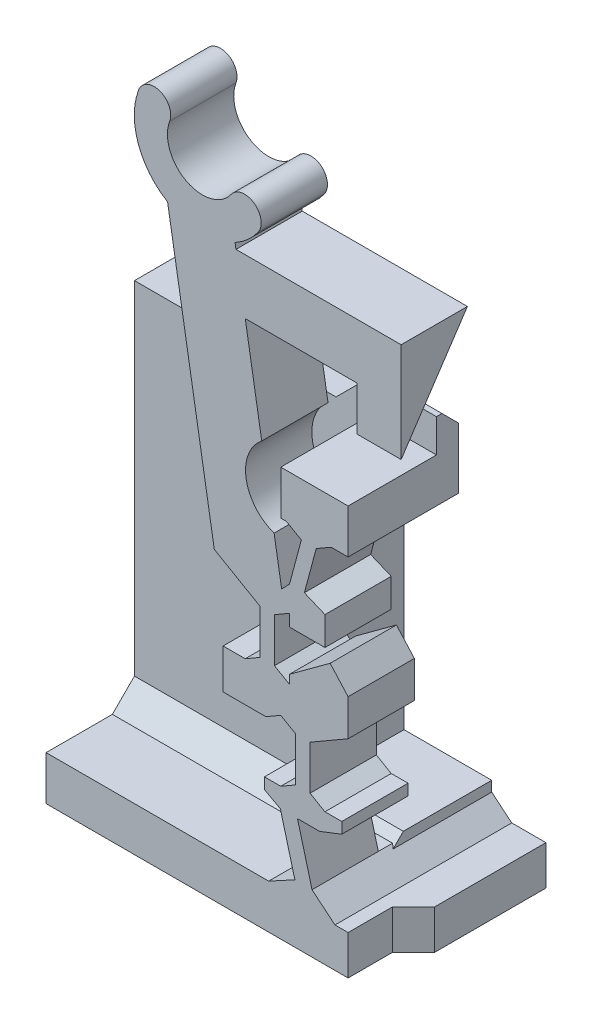
SolidWorks part; units mm, degrees
material "Nylon 6/12"
ref_plane "Front Plane" through (0, 0, 0) normal (0, 0, 1) x (1, 0, 0)
ref_plane "Top Plane" through (0, 0, 0) normal (0, 1, 0) x (1, 0, 0)
ref_plane "Right Plane" through (0, 0, 0) normal (1, 0, 0) x (0, 0, -1)
sketch "Sketch-SkeletonConfigUp" plane through (0, 0, 0) normal (0, 0, 1) x (1, 0, 0)
  line L0 (0, 0) -> (0, -50000) construction
  line L1 (0, 0) -> (4.5811, 6.2164) construction
  line L2 (9.8143, 13.3177) -> (4.5811, 13.945) construction
  line L3 (4.5811, 13.945) -> (2.9713, 10.4094) construction
  line L4 (2.9713, 10.4094) -> (4.5811, 6.2164) construction
  line L5 (4.5811, 13.945) -> (6.2429, 19.1409) construction
  line L6 (2.9713, 10.4094) -> (0.0405, 27.8193) construction
  line L7 (4.5811, 6.2164) -> (9.8143, 13.3177) construction
  line L8 (-587.3593, -797.0242) -> (9.8143, 13.3177) construction
  dimension "D2" = 7.7221
  dimension "D3" = 8.8212
  dimension "D4" = 5.2707
  dimension "D5" = 119.553
  dimension "D6" = 3.8848
  dimension "D7" = 5.4552
  dimension "D8" = 17.6549
  dimension "D9" = 4.4914
  dimension "D10" = 6.745
  dimension "D11" = 145.964
  dimension "D12" = 143.612
sketch "Sketch-SkeletonConfigDown" plane through (0, 0, 0) normal (0, 0, 1) x (1, 0, 0)
  line L0 (0, 0) -> (0, -50000) construction
  line L1 (0, 0) -> (4.5811, 6.2164) construction
  line L2 (9.8143, 13.3177) -> (4.5811, 13.945) construction
  line L3 (4.5811, 13.945) -> (6.1909, 10.4094) construction
  line L4 (6.1909, 10.4094) -> (4.5811, 6.2164) construction
  line L5 (4.5811, 13.945) -> (1.753, 18.6098) construction
  line L6 (6.1909, 10.4094) -> (-8.8652, 19.6294) construction
  line L7 (4.5811, 6.2164) -> (9.8143, 13.3177) construction
  line L8 (-589.9357, -800.5203) -> (9.8143, 13.3177) construction
  dimension "D2" = 7.7221
  dimension "D3" = 8.8212
  dimension "D4" = 5.2707
  dimension "D5" = 119.553
  dimension "D6" = 3.8848
  dimension "D7" = 5.4552
  dimension "D8" = 17.6549
  dimension "D9" = 4.4914
  dimension "D10" = 6.745
  dimension "D11" = 145.964
  dimension "D1" = 143.612
ref_plane "Plane-Cam Base" through (9.128, 0, 0) normal (1, 0, 0) x (0, 0, -1)
ref_plane "Plane-Down-to-Up Derailleur Clearance" through (6.628, 0, 0) normal (1, 0, 0) x (0, 0, -1)
ref_plane "Plane-Cam Cavity Roof" through (5.128, 0, 0) normal (1, 0, 0) x (0, 0, -1)
sketch "Sketch-SwitchBossUp" plane through (0, 0, 0) normal (0, 0, 1) x (1, 0, 0)
  line L0 (3.5811, 11.4759) -> (3.5811, 12.945) construction
  line L5 (5.5811, 12.5552) -> (5.5811, 11.263)
  line L7 (1.5115, 25.1048) -> (1.5536, 24.8548)
  line L8 (-0.4607, 24.7728) -> (1.6966, 11.9577) construction
  line L9 (2.9713, 10.4094) -> (0.0405, 27.8193) construction
  line L11 (0.1364, 21.2256) -> (2.1086, 21.5576) construction
  line L15 (6.628, -23.7286) -> (6.628, 23.7286) construction
  line L16 (2.9713, 10.4094) -> (4.5811, 6.2164) construction
  line L17 (3.5811, 12.945) -> (3.5811, 14.945) construction
  line L18 (5.5811, 12.945) -> (5.5811, 14.945) construction
  line L19 (4.2561, 13.945) -> (4.9061, 13.945) construction
  line L20 (3.5811, 14.945) -> (5.5811, 14.945) construction
  line L21 (3.5811, 12.945) -> (5.5811, 12.945) construction
  line L22 (4.5811, 12.945) -> (4.5811, 14.945) construction
  line L23 (4.5811, 6.2164) -> (8.5405, 7.1023) construction
  line L24 (1.9713, 9.4094) -> (1.9713, 11.4094) construction
  line L25 (3.9713, 9.4094) -> (3.9713, 11.4094) construction
  line L26 (3.9713, 9.4094) -> (1.9713, 9.4094) construction
  line L27 (1.9713, 11.4094) -> (3.9713, 11.4094) construction
  line L28 (3.5811, 7.2164) -> (5.5811, 7.2164) construction
  line L29 (3.5811, 7.2164) -> (3.5811, 5.2164) construction
  line L30 (5.5811, 7.2164) -> (5.5811, 5.2164) construction
  line L31 (3.5811, 5.2164) -> (5.5811, 5.2164) construction
  line L32 (4.9061, 6.2164) -> (4.2561, 6.2164) construction
  line L40 (3.2963, 10.4094) -> (2.6463, 10.4094) construction
  line L66 (0.0405, 27.8193) -> (0.0405, 50027.8193) construction
  line L75 (3.95, 3.937) -> (4.6085, 1.4797) construction
  line L76 (5.5811, 11.263) -> (5.5811, 12.5552) construction
  line L77 (5.5811, 7.6061) -> (6.628, 8.2105)
  line L80 (5.8152, 10.763) -> (6.628, 9.8603)
  line L81 (9.128, 1033.2419) -> (9.128, 20.0586) construction
  line L85 (6.9307, 9.5241) -> (8.5405, 7.7363) construction
  line L88 (5.7256, 17.3347) -> (6.628, 17.3347)
  line L92 (3.7762, 8.3129) -> (6.9307, 9.5241) construction
  line L98 (1.9713, 9.0197) -> (0.9713, 9.0197)
  line L99 (0.9713, 9.0197) -> (0.9713, 7.2164)
  line L100 (0.9713, 7.2164) -> (2.9061, 7.2164)
  line L101 (4.5811, 6.2164) -> (6.9307, 9.5241) construction
  line L103 (0.0405, 27.8193) -> (1.9448, 26.4638) construction
  line L104 (6.9307, 9.5241) -> (8.5405, 7.7363) construction
  line L107 (1.9713, 9.4094) -> (1.9713, 9.0197) construction
  line L109 (0.0405, 27.8193) -> (-2.1498, 28.6358) construction
  line L111 (6.628, 9.8603) -> (6.628, 8.2105)
  line L112 (6.628, 9.8603) -> (6.9307, 9.5241) construction
  line L113 (2.8424, 4.8267) -> (2.8424, 4.3267)
  line L114 (7.3693, 7.7363) -> (7.3563, 7.7363) construction
  line L121 (4.9967, -1.1226) -> (4.9967, 1.4797) construction
  line L122 (9.028, 22.3548) -> (9.028, 20.3548)
  line L127 (5.5811, 15.3347) -> (5.5811, 14.945) construction
  line L130 (6.0345, 0.6165) -> (6.628, 0.6165)
  line L132 (2.8424, 4.3267) -> (3.5618, 3.937)
  line L133 (2.9713, 10.4094) -> (6.1909, 10.4094) construction
  line L134 (4.5811, 10.4094) -> (4.5811, 13.945) construction
  line L135 (4.5811, 10.4094) -> (4.5811, 6.2164) construction
  line L137 (3.9713, 9.4094) -> (5.5811, 7.2164) construction
  line L139 (5.8152, 10.763) -> (3.9713, 9.4094)
  line L141 (4.2202, 1.4797) -> (3.0345, 0.8347)
  line L142 (3.0345, 0.8347) -> (3.0345, -1.1653)
  line L143 (9.128, 20.0586) -> (9.128, 18.3333) construction
  line L145 (9.128, 16.6071) -> (9.128, -49992.4167) construction
  line L147 (5.5811, 11.263) -> (5.5811, 12.5552) construction
  line L150 (3.0345, -1.1653) -> (6.628, -1.1653)
  line L151 (3.5618, 3.937) -> (4.3383, 3.937) construction
  line L152 (4.5126, 14.945) -> (3.9767, 12.945)
  line L153 (5.1855, 14.945) -> (4.6496, 12.945)
  line L157 (3.5811, 17.3347) -> (3.5811, 15.3347)
  line L158 (5.8605, 15.3347) -> (6.628, 15.3347)
  line L162 (3.2963, 11.4094) -> (3.2963, 9.4094)
  line L164 (2.6463, 11.4094) -> (2.6463, 9.4094)
  line L169 (4.2561, 7.2164) -> (4.2561, 5.2164)
  line L170 (4.9061, 5.2164) -> (4.9061, 7.2164)
  line L175 (4.2561, 7.2164) -> (3.5811, 7.6061)
  line L176 (4.9061, 7.2164) -> (5.5811, 7.6061)
  line L177 (5.5811, 7.2164) -> (5.5811, 7.6061) construction
  line L179 (4.2561, 5.2164) -> (3.5811, 4.8267)
  line L180 (3.5811, 5.2164) -> (3.5811, 4.8267) construction
  line L181 (3.5811, 4.8267) -> (2.8424, 4.8267)
  line L183 (4.9061, 5.2164) -> (5.5811, 4.8267)
  line L184 (5.5811, 5.2164) -> (5.5811, 4.8267) construction
  line L186 (9.128, -23.7286) -> (9.128, 23.7286) construction
  line L187 (2.6463, 9.4094) -> (1.9713, 9.0197)
  line L188 (3.2963, 9.4094) -> (3.9713, 9.0197)
  line L189 (3.2963, 11.4094) -> (3.9713, 11.7991)
  line L190 (2.6463, 11.4094) -> (1.6966, 11.9577)
  line L191 (3.9713, 11.4094) -> (3.9713, 11.7991) construction
  line L192 (3.9713, 11.7991) -> (3.9713, 11.263)
  line L193 (4.6496, 12.945) -> (5.5811, 12.5552)
  line L194 (3.9767, 12.945) -> (3.6203, 12.5779)
  line L195 (3.9713, 11.263) -> (5.5811, 11.263)
  line L196 (3.9713, 9.4094) -> (3.9713, 9.0197)
  line L197 (3.5811, 7.2164) -> (3.5811, 7.6061) construction
  line L199 (3.5811, 7.6061) -> (2.9061, 7.2164)
  line L201 (2.8424, 4.3267) -> (2.8424, 3.937) construction
  line L202 (2.8424, 3.937) -> (3.5618, 3.937) construction
  line L205 (3.0345, 1.4797) -> (3.0345, 0.8347) construction
  line L206 (4.9967, 1.4797) -> (6.0345, 0.6165)
  line L207 (9.128, 18.3333) -> (9.128, 16.6071) construction
  line L208 (6.628, -1.1653) -> (6.628, 0.6165)
  line L209 (9.128, 20.0586) -> (9.128, 16.6071) construction
  line L211 (4.9967, 1.4797) -> (4.3383, 3.937)
  line L212 (4.2202, 1.4797) -> (3.5618, 3.937)
  line L214 (4.5126, 14.945) -> (3.8375, 15.3347)
  line L215 (3.8375, 15.3347) -> (3.5811, 15.3347)
  line L216 (5.1855, 14.945) -> (5.8605, 15.3347)
  line L217 (5.5811, 12.945) -> (5.5811, 12.5552) construction
  line L218 (5.1855, 14.945) -> (5.1855, 15.3347) construction
  line L219 (5.8605, 15.3347) -> (3.8375, 15.3347) construction
  line L221 (9.028, 22.3548) -> (9.028, 24.8548)
  line L224 (3.5811, 17.3347) -> (5.7256, 17.3347)
  line L232 (6.628, 15.3347) -> (6.628, 17.3347)
  line L236 (1.5536, 24.8548) -> (9.028, 24.8548)
  line L240 (4.3383, 3.937) -> (5.3383, 3.937)
  line L241 (5.3383, 3.937) -> (6.3424, 4.3267)
  line L248 (7.028, 22.3548) -> (1.9744, 22.3548)
  line L249 (1.9744, 22.3548) -> (2.7198, 17.9273)
  line L250 (9.028, 20.3548) -> (7.028, 20.3548)
  line L251 (7.028, 20.3548) -> (7.028, 22.3548)
  line L252 (3.2801, 14.5986) -> (3.6203, 12.5779)
  line L253 (4.2672, 14.0291) -> (4.895, 13.8608) construction
  line L254 (4.9967, 1.4797) -> (4.2202, 1.4797) construction
  line L255 (4.2202, 1.4797) -> (3.0345, 1.4797) construction
  line L256 (1.6966, 11.9577) -> (0.5733, 12.6062)
  line L257 (0.5733, 12.6062) -> (-1.5413, 25.1678)
  line L367 (5.5811, 4.8267) -> (6.3424, 4.8267)
  line L368 (6.3424, 4.8267) -> (6.3424, 4.3267)
  arc A0 (1.5115, 25.1048) -> (2.5558, 26.0289) centre (0.0405, 27.8193) ccw
  arc A1 (-1.5413, 25.1678) -> (-2.8525, 28.8978) centre (0.0405, 27.8193) cw
  arc A2 (-2.8525, 28.8978) -> (-1.447, 28.3738) centre (-2.1498, 28.6358) cw
  arc A3 (2.5558, 26.0289) -> (1.3338, 26.8987) centre (1.9448, 26.4638) ccw
  arc A4 (-1.447, 28.3738) -> (1.3338, 26.8987) centre (0.0405, 27.8193) ccw
  arc A5 (3.5811, 12.945) -> (3.5811, 14.945) centre (3.1778, 13.945) ccw construction
  arc A6 (5.5811, 12.945) -> (5.5811, 14.945) centre (5.9843, 13.945) cw construction
  arc A7 (2.5293, 9.921) -> (1.9713, 11.4094) centre (1.568, 10.4094) ccw construction
  arc A8 (3.9713, 11.4094) -> (3.9713, 9.4094) centre (4.3745, 10.4094) ccw construction
  arc A9 (3.5811, 7.2164) -> (3.5811, 5.2164) centre (3.1779, 6.2164) cw construction
  arc A10 (5.5811, 7.2164) -> (5.5811, 5.2164) centre (5.9844, 6.2164) ccw construction
  circle A28 centre (0.0405, 27.8193) radius 2.3375 construction
  arc A29 (1.9713, 9.4094) -> (2.5293, 9.921) centre (1.568, 10.4094) ccw construction
  arc A30 (3.2801, 14.5986) -> (2.7198, 17.9273) centre (3.9114, 16.4164) cw
  arc A31 (-0.4607, 24.7728) -> (-1.5413, 25.1678) centre (0.0405, 27.8193) cw construction
  point P53 (4.5811, 13.945)
  point P63 (2.9713, 10.4094)
  point P93 (1.1225, 21.3916)
  dimension "D23" = 1.5875
  dimension "D24" = 0.75
  dimension "D2" = 2
  dimension "D5" = 2
  dimension "D8" = 42
  dimension "D16" = 42
  dimension "D27" = 120
  dimension "D28" = 120
  dimension "D29" = 120
  dimension "D30" = 120
  dimension "D31" = 120
  dimension "D32" = 120
  dimension "D33" = 120
  dimension "D34" = 120
  dimension "D17" = 0.5
  dimension "D21" = 2
  dimension "D38" = 2
  dimension "D39" = 0.5
  dimension "D40" = 60
  dimension "D41" = 1
  dimension "D42" = 45
  dimension "D43" = 120
  dimension "D10" = 15
  dimension "D25" = 15
  dimension "D26" = 120
  dimension "D35" = 120
  dimension "D20" = 3
  dimension "D48" = 2
  dimension "D82" = 1
  dimension "D83" = 3.5
  dimension "D14" = 2.5
  dimension "D15" = 0.25
  dimension "D7" = 2
  dimension "D9" = 2
  dimension "D6" = 0.65
  dimension "D12" = 0.75
  dimension "D13" = 1
extrude "Boss-Switch Body" add sketch "Sketch-SwitchBossUp" along normal blind 3
sketch "Sketch1" plane through (0, 0, 0) normal (0, 0, -1) x (-1, 0, 0)
  line L1 (-7.5811, -1.1653) -> (0.4122, -1.1653)
  line L2 (-7.5811, -1.1653) -> (-7.5811, 0.6165)
  line L4 (0.4122, -1.1653) -> (0.4122, 0.8347)
  line L5 (-3.5811, 18.8347) -> (-7.5811, 18.8347)
  line L10 (-7.5811, 18.8347) -> (-7.5811, 15.3347)
  line L11 (-4.2202, 1.4797) -> (-4.9967, 1.4797)
  line L12 (-7.5811, 15.3347) -> (-3.5811, 15.3347)
  line L13 (-4.2202, 1.4797) -> (-3.0345, 0.8347)
  line L14 (-3.5811, 15.3347) -> (-3.5811, 18.8347)
  line L20 (-4.3383, 3.937) -> (-4.9967, 1.4797) construction
  line L22 (-3.0345, -1.1653) -> (-6.628, -1.1653) construction
  line L23 (-3.0345, 0.8347) -> (0.4122, 0.8347)
  line L24 (-4.9967, 1.4797) -> (-6.0345, 0.6165)
  line L25 (-6.0345, 0.6165) -> (-7.5811, 0.6165)
  dimension "D1" = 3.5
extrude "Boss-Flange Width" add sketch "Sketch1" along normal blind 5
ref_plane "Plane-Sta2Sit Groove" through (0.0405, 0, 0) normal (1, 0, 0) x (0, 0, -1)
ref_plane "Plane-Cam Outer Surface" through (-12.0395, 0, 0) normal (1, 0, 0) x (0, 0, -1)
ref_plane "Plane-FlangeTop" through (-7.0395, 0, 0) normal (1, 0, 0) x (0, 0, -1)
sketch "Sketch2" plane through (-7.0395, 0, 0) normal (1, 0, 0) x (0, 0, -1)
  line L0 (5, 15.3347) -> (-3, 15.3347) construction
  line L1 (5, 17.3347) -> (1, 17.3347)
  line L2 (5, 17.3347) -> (5, 15.3347)
  line L3 (5, 15.3347) -> (1, 15.3347)
  line L4 (1, 17.3347) -> (1, 15.3347)
  line L5 (-3, -1.1653) -> (-3, 0.6165) construction
  line L11 (5, 0.8347) -> (-3, 0.8347)
  line L12 (5, 0.8347) -> (5, -1.1653)
  line L13 (5, -1.1653) -> (-3, -1.1653)
  line L14 (-3, 0.8347) -> (-3, -1.1653)
  line L15 (0, 10.4094) -> (0, 27.8193) construction
  line L17 (5, 0.6165) -> (5, -1.1653) construction
  line L18 (-3, 0.8347) -> (0, 0.8347) construction
  dimension "D1" = 1
  dimension "D2" = 2
extrude "Boss-Flange Height" add sketch "Sketch2" along normal up to surface (11.6675 mm away)
sketch "Sketch10" plane through (0, 15.3347, 0) normal (0, 1, 0) x (1, 0, 0)
  line L0 (9.128, -23.7286) -> (9.128, 23.7286) construction
  line L1 (7.5811, 5) -> (5.128, 5)
  line L2 (7.5811, 5) -> (7.5811, 2)
  line L3 (7.5811, 2) -> (5.128, 2)
  line L5 (4.628, 7) -> (4.628, 1) construction
  line L6 (3.5811, 1) -> (-7.0395, 1) construction
  line L8 (5.128, 5) -> (5.128, 2)
  dimension "D1" = 1
  dimension "D2" = 0.5
  dimension "D3" = 4.5
extrude "Cut-Up-To-Down Derailleur Clearance" cut sketch "Sketch10" along normal up to next
sketch "Sketch17" plane through (0, 15.3347, 0) normal (0, -1, 0) x (1, 0, 0)
  line L0 (5.128, -5) -> (-7.0395, -5)
  line L1 (5.128, -5) -> (-7.0395, -5) construction
  line L2 (-7.0395, -5) -> (-7.0395, -1)
  line L3 (-7.0395, -1) -> (5.128, -1)
  line L4 (5.128, -1) -> (5.128, -5)
  line L5 (-7.0395, -1) -> (-7.0395, -5) construction
extrude "Boss-Flange Support" add sketch "Sketch17" along normal up to surface (14.5 mm away) up to face at (-2.0025, 0.8347, -1)
sketch "Sketch-HolePositions" plane through (0, -1.1653, 0) normal (0, -1, 0) x (1, 0, 0)
  line L0 (-7.0395, -3) -> (7.5811, -3) construction
  line L1 (7.5811, -5) -> (-7.0395, -5) construction
  line L2 (7.5811, -5) -> (7.5811, 0) construction
  line L4 (-7.0395, -22.2167) -> (-7.0395, 22.2167) construction
  point P6 (-5.0395, -3)
  point P7 (-0.5395, -3)
  dimension "D1" = 2
  dimension "D2" = 4.5
  dimension "D3" = 2
sketch "Sketch6" plane through (0, -1.1653, 0) normal (0, -1, 0) x (-1, 0, 0)
  point P0 (5.0395, 3)
  point P3 (0.5395, 3)
hole_wizard "Tap Drill for M2x0.4 Tap1" positions "Sketch6" profile "Sketch5" hole size "M2x0.4" standard "ANSI Metric" end condition through all
sketch "Sketch5" plane through (-5.0395, -1.1653, -3) normal (1, 0, 0) x (0, 0, -1)
  line L0 (0, 0) -> (0, 30.5511)
  line L1 (0, 30.5511) -> (0.8, 30.5511)
  line L2 (0.8, 30.5511) -> (0.8, 0)
  line L5 (0.8, 0) -> (0, 0)
  line L11 (0, -6.35) -> (0, 107.95) construction
  dimension "Thru Hole Dia." = 1.6
  dimension "Thru Hole Depth" = 30.5511
sketch "Sketch9" plane through (0, -1.1653, 0) normal (0, -1, 0) x (1, 0, 0)
  point P0 (-5.0395, -3)
  point P3 (-0.5395, -3)
hole_wizard "M2 Clearance Hole2" positions "Sketch9" profile "Sketch8" hole size "M2" standard "ANSI Metric"
sketch "Sketch8" plane through (-5.0395, -1.1653, -3) normal (1, 0, 0) x (0, 0, -1)
  line L0 (0, 0) -> (0, 15.721)
  line L1 (0, 15.721) -> (1.2, 15)
  line L2 (1.2, 15) -> (1.2, 0)
  line L5 (1.2, 0) -> (0, 0)
  line L10 (0, 15.721) -> (-1.2, 15) construction
  line L11 (0, -6.35) -> (0, 107.95) construction
  dimension "Hole Dia." = 2.4
  dimension "Hole Depth" = 15
  dimension "Drill Angle" = 118
sketch "Sketch-Measurements for Derailleur Ramps" [suppressed] plane through (0, 0, 0) normal (0, 0, 1) x (1, 0, 0)
  line L0 (3.184, 15.1695) -> (2.4687, 19.4188)
  line L1 (2.8264, 17.2941) -> (1.8402, 17.1281)
  line L2 (2.9713, 10.4094) -> (0.0405, 27.8193) construction
  line L3 (1.8402, 17.1281) -> (-1.3081, 15.0016)
  line L4 (6.1909, 10.4094) -> (-8.8652, 19.6294) construction
  line L5 (1.8402, 17.1281) -> (2.6012, 12.6077)
  line L6 (2.6012, 12.6077) -> (-1.3081, 15.0016)
  line L7 (0.2661, 16.0649) -> (0.2661, 17.1281)
  line L8 (0.2661, 17.1281) -> (1.8402, 17.1281)
  line L9 (6.1909, 10.4094) -> (2.9713, 10.4094)
  line L10 (5.386, 8.3129) -> (3.7762, 8.3129)
  line L11 (2.6116, 18.5698) -> (1.5115, 25.1048) construction
  line L12 (6.1909, 10.4094) -> (4.5811, 6.2164) construction
  line L13 (4.5811, 8.3129) -> (4.5811, 8.7912)
  line L14 (4.5811, 6.2164) -> (5.386, 8.3129)
  line L15 (2.9713, 10.4094) -> (4.5811, 6.2164) construction
  line L16 (3.7762, 8.3129) -> (4.5811, 6.2164)
  line L17 (5.386, 8.3129) -> (5.386, 8.7912)
  dimension "D1" = 1.5742
  dimension "D2" = 0.8049
ref_plane "Plane1" through (0, 7.1023, 0) normal (0, 1, 0) x (1, 0, 0)
ref_plane "Plane-Cantilever Cut" [suppressed] through (7.0848, 8.5204, -1.9058) normal (-0.6301, -0.7578, 0.1695) x (-0.7765, 0.6151, -0.1368)
sketch "Sketch14" [suppressed] plane through (7.0848, 8.5204, -1.9058) normal (-0.6301, -0.7578, 0.1695) x (-0.7765, 0.6151, -0.1368)
  line L0 (2.3023, -1.6911) -> (-0.3551, -1.6911)
  line L2 (2.3023, -4.3362) -> (2.3023, -1.6911)
  line L3 (-0.3551, -1.6911) -> (-0.3551, -4.4608)
  line L5 (-0.3551, -4.4608) -> (1.0087, -5.0843)
  line L6 (1.0087, -5.0843) -> (2.3023, -4.3362)
extrude "Cut-Down-to-Up Cantilever Slope" [suppressed] cut sketch "Sketch14" against normal up to next
ref_plane "Plane-Symmetry Plane" through (0, 0, 1.5) normal (0, 0, 1) x (1, 0, 0)
sketch "Sketch-Cable Center Point" plane through (0, 0, 1.5) normal (0, 0, 1) x (1, 0, 0)
  line L0 (0.0405, 27.8193) -> (0.1722, 27.0366)
  line L1 (2.9713, 10.4094) -> (0.0405, 27.8193) construction
  point P0 (0.0405, 27.8193)
  dimension "D1" = 0.7937
chamfer "Chamfer-Flange Support" distance 1.5 angle 45 1 edges at (3.5811, 17.3347, -3)
chamfer "Chamfer-Flange Support 2" distance 1.5 angle 45 2 edges at (5.128, 17.0847, -2) (5.128, 15.3347, -1.5)
chamfer "Chamfer-Flange Support 3" distance 1 angle 45 1 edges at (-2.0025, 0.8347, -1)
chamfer "Chamfer7" [suppressed] distance 1 angle 45
sketch "Sketch23" plane through (0, 0, -1) normal (0, 0, 1) x (1, 0, 0)
  line L0 (5.128, 1.8347) -> (1.1605, 1.8347)
  line L1 (-7.0395, 1.8347) -> (5.128, 1.8347) construction
  line L2 (1.1605, 1.8347) -> (1.1605, 13.8347)
  line L3 (1.1605, 13.8347) -> (5.128, 13.8347)
  line L4 (5.128, 13.8347) -> (5.128, 1.8347)
  line L5 (0.6605, -1.1653) -> (0.6605, 13.8347) construction
  dimension "D1" = 0.5
extrude "Cut-Gap for Printing" cut sketch "Sketch23" against normal through all
sketch "Sketch25" plane through (0, 0, 0) normal (0, 0, 1) x (1, 0, 0)
  line L0 (6.628, 15.3347) -> (7.5811, 15.3347)
  line L1 (7.5811, 15.3347) -> (7.5811, 18.8347)
  line L2 (7.5811, 18.8347) -> (6.628, 18.8347)
  line L3 (6.628, -23.7286) -> (6.628, 23.7286) construction
  line L4 (7.5811, 18.8347) -> (3.5811, 18.8347) construction
  line L5 (6.628, 18.8347) -> (6.628, 15.3347)
  line L6 (7.5811, 18.8347) -> (7.5811, 15.3347) construction
extrude "Cut-Derailleur Clearance" cut sketch "Sketch25" against normal through all
chamfer "Chamfer8" distance 1 angle 45 1 edges at (6.628, -0.2744, 0)
ref_plane "Plane2" through (-3.0866, 5.589, 8.3835) normal (0.2929, -0.5304, -0.7956) x (-0.9561, -0.1625, -0.2437)
sketch "Sketch26" plane through (-3.0866, 5.589, 8.3835) normal (0.2929, -0.5304, -0.7956) x (-0.9561, -0.1625, -0.2437)
  line L0 (-7.553, 20.6804) -> (-7.553, 14.9094)
  line L1 (-12.6703, 20.6804) -> (-5.5238, 20.6804) construction
  line L3 (-7.553, 14.9094) -> (-20.0302, 14.9094)
  line L4 (-20.0302, 14.9094) -> (-20.0302, 20.6804)
  line L5 (-20.0302, 20.6804) -> (-7.553, 20.6804)
extrude "Cut-Up-to-Down Cantilever Slope" cut sketch "Sketch26" along normal up to next
sketch "Sketch27" plane through (5.128, 0, 0) normal (1, 0, 0) x (0, 0, -1)
  line L0 (3.5, 18.8347) -> (3.5, 13.8347) construction
  line L1 (2.5, 18.8347) -> (5, 18.8347)
  line L2 (2.5, 18.8347) -> (2.5, 13.8347)
  line L3 (2.5, 13.8347) -> (5, 13.8347)
  line L4 (5, 18.8347) -> (5, 13.8347)
  dimension "D1" = 1
extrude "Cut-Wide Derailleur Clearance" cut sketch "Sketch27" against normal blind 4 and the other way through all
chamfer "Chamfer9" distance 1.25 angle 45 1 edges at (4.8545, 18.8347, -2.5)
sketch "Sketch28" plane through (0, 0, -1) normal (0, 0, 1) x (1, 0, 0)
  line L0 (3.5811, 18.8347) -> (6.628, 18.8347)
  line L1 (6.628, 18.8347) -> (6.628, 17.3347)
  line L2 (6.628, 17.3347) -> (3.5811, 17.3347)
  line L3 (3.5811, 17.3347) -> (3.5811, 18.8347)
extrude "Cut-Extrude1" cut sketch "Sketch28" along normal up to surface (1 mm away) up to face at (5.1045, 18.0847, 0)
equation "\"axle-diameter\"=2"
equation "\"switch-thickness\"=12"
equation "\"base-width\"=4.0"
equation "\"axle-bushing-radius\"=3"
equation "\"clearance\"= 0.25"
equation "\"arm-width\"=1.5"
equation "\"min-diameter\"=70"
equation "\"alpha\"=143.6120"
equation "\"gamma\"=119.5526"
equation "\"delta\"=145.9637"
equation "\"epsilon\"=6.7452"
equation "\"l_AB\"=8.8212"
equation "\"l_AC\"=4.4914"
equation "\"l_BD\"=5.2707"
equation "\"l_CD\"=3.8848"
equation "\"l_CE\"=17.6549"
equation "\"l_DF\"=5.4552"
equation "\"l_OA\"=7.7221"
equation "\"D2@Sketch-SkeletonConfigUp\" = \"l_OA\""
equation "\"D3@Sketch-SkeletonConfigUp\" = \"l_AB\""
equation "\"D4@Sketch-SkeletonConfigUp\" = \"l_BD\""
equation "\"D5@Sketch-SkeletonConfigUp\" = \"gamma\""
equation "\"D6@Sketch-SkeletonConfigUp\" = \"l_CD\""
equation "\"D7@Sketch-SkeletonConfigUp\" = \"l_DF\""
equation "\"D8@Sketch-SkeletonConfigUp\" = \"l_CE\""
equation "\"D9@Sketch-SkeletonConfigUp\" = \"l_AC\""
equation "\"D_groove\"=3.175"
equation "\"D7@Sketch-SkeletonConfigDown\" = \"l_DF\""
equation "\"D6@Sketch-SkeletonConfigDown\" = \"l_CD\""
equation "\"D2@Sketch-SkeletonConfigDown\" = \"l_OA\""
equation "\"D3@Sketch-SkeletonConfigDown\" = \"l_AB\""
equation "\"D9@Sketch-SkeletonConfigDown\" = \"l_AC\""
equation "\"D8@Sketch-SkeletonConfigDown\" = \"l_CE\""
equation "\"D5@Sketch-SkeletonConfigDown\" = \"gamma\""
equation "\"D4@Sketch-SkeletonConfigDown\" = \"l_BD\""
equation "\"D1@Sketch-SkeletonConfigDown\" = \"alpha\""
equation "\"hinge_length\"=1.5"
equation "\"hinge_depth\"=0.25"
equation "\"D10@Sketch-SkeletonConfigUp\"=\"epsilon\""
equation "\"D11@Sketch-SkeletonConfigUp\"=\"delta\""
equation "\"D12@Sketch-SkeletonConfigUp\"=\"alpha\""
equation "\"D11@Sketch-SkeletonConfigDown\"=\"delta\""
equation "\"D10@Sketch-SkeletonConfigDown\"=\"epsilon\""
equation "\"EE_dx\"=8.9056"
equation "\"EE_dy\"=8.1898"
equation "\"r_groove\"=\"D_groove\"/2"
equation "\"t_wall\"=25.4/16"
equation "\"width_lower\"=\"D_groove\"+\"t_wall\""
equation "\"cable_to_bottom\"=30.6257"
equation "\"switch_EE-up_base_dy\"=24"
equation "\"switch_EE-down_base_dy\"=16"
equation "\"D_axle\"=25.4/8"
equation "\"D_up_to_down\"=16"
equation "\"D_down_to_up\"=25"
equation "\"t_cam_base\"=7.5"
equation "\"D23@Sketch-SwitchBossUp\"=\"D_groove\"/2"
equation "\"D1@Sketch-Cable Center Point\"=\"D_groove\"/4"
